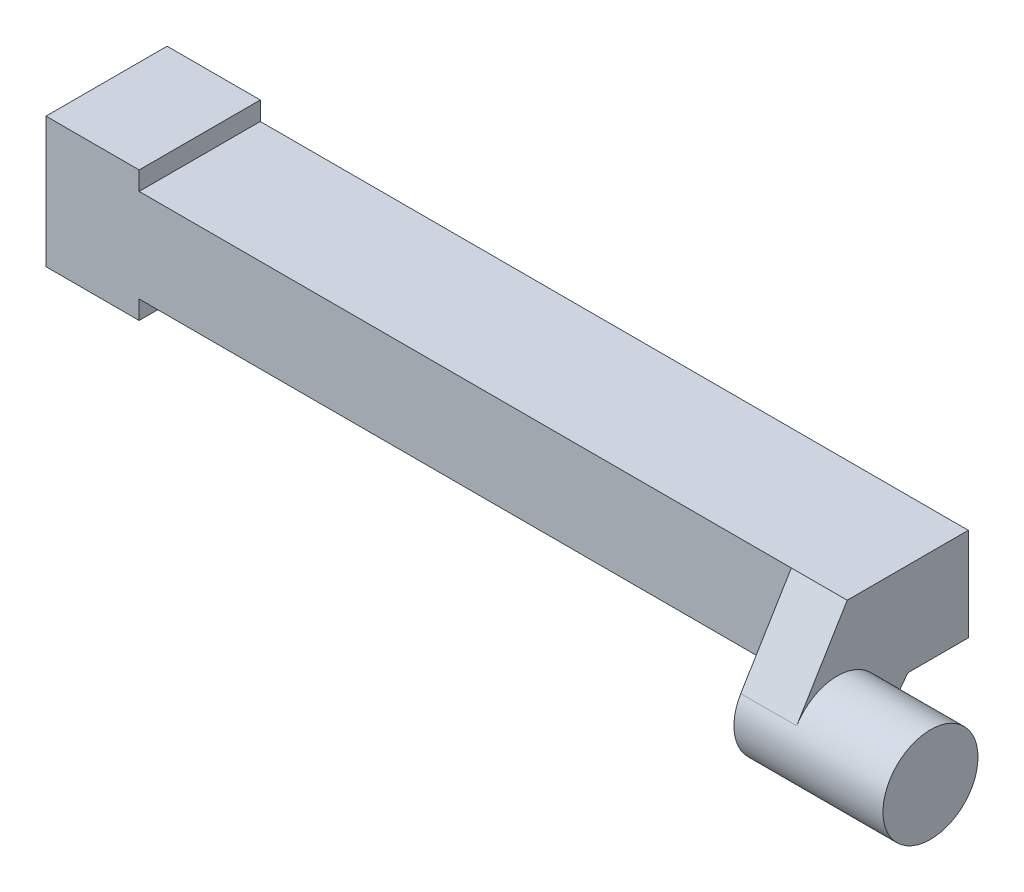
SolidWorks part; units mm, degrees
ref_plane "Front Plane" through (0, 0, 0) normal (0, 0, 1) x (1, 0, 0)
ref_plane "Top Plane" through (0, 0, 0) normal (0, 1, 0) x (1, 0, 0)
ref_plane "Right Plane" through (0, 0, 0) normal (1, 0, 0) x (0, 0, -1)
sketch "Sketch2" plane through (0, 0, 0) normal (1, 0, 0) x (0, 0, -1)
  line L1 (-2.25, -2.25) -> (2.25, -2.25)
  line L2 (-2.25, -2.25) -> (-2.25, 2.25)
  line L3 (-2.25, 2.25) -> (2.25, 2.25)
  line L4 (2.25, -2.25) -> (2.25, 2.25)
  line L5 (-2.25, -2.25) -> (2.25, 2.25) construction
  line L6 (-2.25, 2.25) -> (2.25, -2.25) construction
  line L7 (3.25, -2.5) -> (-3.25, -2.5)
  line L8 (3.25, -2.5) -> (3.25, 2.5)
  line L9 (3.25, 2.5) -> (-3.25, 2.5)
  line L10 (-3.25, -2.5) -> (-3.25, 2.5)
  line L11 (3.25, -2.5) -> (-3.25, 2.5) construction
  line L12 (3.25, 2.5) -> (-3.25, -2.5) construction
  point P0 (0, 0)
  point P5 (0, 0)
  dimension "D1" = 4.5
  dimension "D2" = 4.5
  dimension "D3" = 6.5
  dimension "D4" = 5
extrude "Boss-Extrude1" add sketch "Sketch2" along normal blind 10
extrude "Boss-Extrude2" add sketch "Sketch2<2>" along normal blind 30 from surface contours L1 L4 L3 L2 | L10 L7 L8 L9 L4 L1 L2 L3 region at (0, 0, 0) region at (0, -2.418, 0) starting at face at (10, 0, 0)
sketch "Sketch2<2>" plane through (0, 0, 0) normal (1, 0, 0) x (0, 0, -1) same geometry as "Sketch2"
sketch "Sketch5" plane through (40, 0, 0) normal (1, 0, 0) x (0, 0, -1)
  line L0 (-0.02, -0.4959) -> (-4.75, -0.4959) construction
  line L5 (-5.9623, -1.983) -> (-3.25, 2.5)
  line L6 (-3.25, 2.5) -> (3.25, 2.5)
  line L7 (3.25, 2.5) -> (3.25, -2.5)
  line L8 (3.25, -2.5) -> (0, -2.5)
  line L9 (-3.25, -2.5) -> (3.25, -2.5) construction
  line L10 (0, -2.5) -> (-1.7367, -4.8278)
  arc A1 (-5.9623, -1.983) -> (-1.7367, -4.8278) centre (-3.7806, -3.303) ccw
  dimension "D2" = 2.55
  dimension "D1" = 4.73
  dimension "D3" = 5
extrude "Boss-Extrude3" add sketch "Sketch5" along normal blind 3
sketch "Sketch6" plane through (43, 0, 0) normal (1, 0, 0) x (0, 0, -1)
  circle A1 centre (-3.7806, -3.303) radius 2.55
  dimension "D1" = 5.1
extrude "Boss-Extrude4" add sketch "Sketch6" along normal blind 5
sketch "Sketch7" plane through (0, 0, 0) normal (-1, 0, 0) x (0, 0, 1)
  line L1 (-3.25, -2.5) -> (3.25, -2.5)
  line L2 (-3.25, -2.5) -> (-3.25, -3.5)
  line L3 (-3.25, -3.5) -> (3.25, -3.5)
  line L4 (3.25, -2.5) -> (3.25, -3.5)
  line L5 (-3.25, 2.5) -> (3.25, 2.5)
  line L6 (-3.25, 2.5) -> (-3.25, 3.5)
  line L7 (-3.25, 3.5) -> (3.25, 3.5)
  line L8 (3.25, 2.5) -> (3.25, 3.5)
  point P10 (0, 0)
  dimension "D1" = 1
  dimension "D2" = 1
extrude "Boss-Extrude5" add sketch "Sketch7" against normal blind 5
